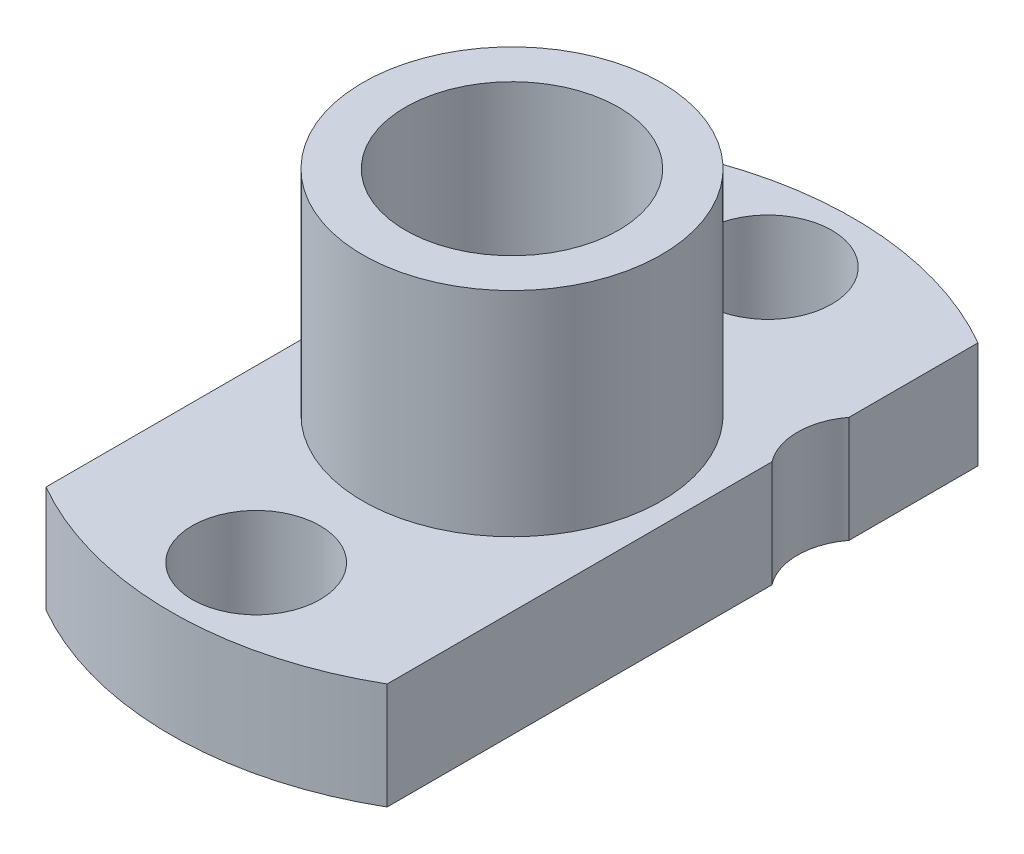
SolidWorks part; units mm, degrees
material "Laiton"
ref_plane "Plan de face" through (0, 0, 0) normal (0, 0, 1) x (1, 0, 0)
ref_plane "Plan de dessus" through (0, 0, 0) normal (0, 1, 0) x (1, 0, 0)
ref_plane "Plan de droite" through (0, 0, 0) normal (1, 0, 0) x (0, 0, -1)
sketch "Esquisse1" plane through (0, 0, 0) normal (0, 0, 1) x (1, 0, 0)
  line L0 (0, 0) -> (0, 7.6852) construction
  line L1 (2.5, 0) -> (8, 0)
  line L2 (8, 0) -> (8, 2.5)
  line L3 (8, 2.5) -> (3.5, 2.5)
  line L4 (3.5, 2.5) -> (3.5, 7.5)
  line L5 (3.5, 7.5) -> (2.5, 7.5)
  line L6 (2.5, 7.5) -> (2.5, 0)
  dimension "D1" = 5
  dimension "D2" = 7
  dimension "D3" = 5
  dimension "D4" = 2.5
  dimension "D5" = 16
revolve "Révolution1" add sketch "Esquisse1" angle 360 about L0
sketch "Esquisse2" plane through (0, 0, 0) normal (0, -1, 0) x (1, 0, 0)
  line L0 (0, 6) -> (5.1962, -3) construction
  line L1 (5.1962, -3) -> (-5.1962, -3) construction
  line L2 (-5.1962, -3) -> (0, 6) construction
  circle A0 centre (0, 0) radius 6 construction
  circle A1 centre (0, 6) radius 1.5
  circle A2 centre (5.1962, -3) radius 1.5
  circle A3 centre (-5.1962, -3) radius 1.5
  circle A4 centre (0, -6) radius 1.5
  dimension "D1" = 3
  dimension "D2" = 12
extrude "Enlèv. mat.-Extru.1" cut sketch "Esquisse2" against normal through all
sketch "Esquisse3" plane through (0, 0, 0) normal (0, -1, 0) x (1, 0, 0)
  line L0 (4, -8) -> (-4, 8) construction
  line L1 (4, -8) -> (-4, -8)
  line L2 (4, -8) -> (4, 8)
  line L3 (4, 8) -> (-4, 8)
  line L4 (-4, -8) -> (-4, 8)
  circle A0 centre (0, 0) radius 8 construction
  point P4 (-3.4289, -10.0228)
  point P5 (0, 0)
  point P6 (-2.2625, 10.025)
  point P8 (-4.3968, 10.4823)
  dimension "D1" = 8
extrude "Enlèv. mat.-Extru.2" cut sketch "Esquisse3" against normal through all flip side to cut
